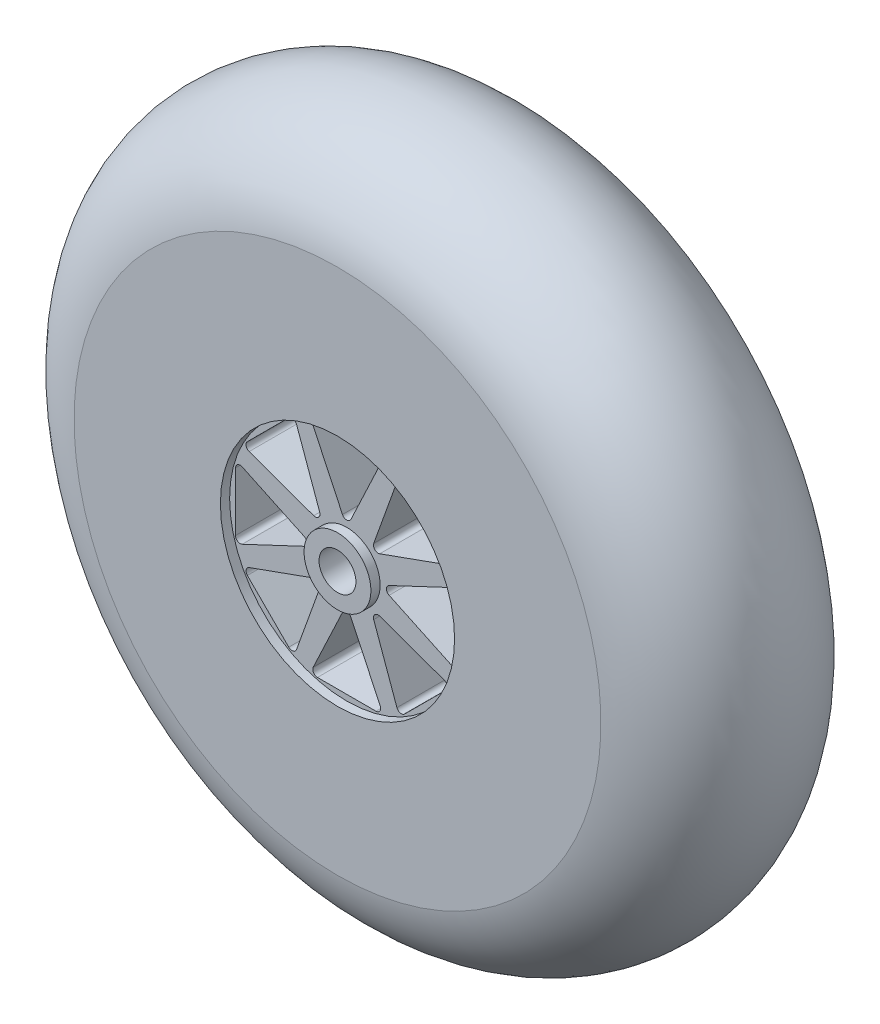
SolidWorks part; units mm, degrees
material "Rubber"
ref_plane "Front Plane" through (0, 0, 0) normal (0, 0, 1) x (1, 0, 0)
ref_plane "Top Plane" through (0, 0, 0) normal (0, 1, 0) x (1, 0, 0)
ref_plane "Right Plane" through (0, 0, 0) normal (1, 0, 0) x (0, 0, -1)
sketch "Sketch1" plane through (0, 0, 0) normal (1, 0, 0) x (0, 0, -1)
  line L0 (0, 28.575) -> (0, 2)
  line L1 (22.225, 28.575) -> (22.225, 2)
  line L2 (11.1125, 38.1) -> (11.1125, 0) construction
  line L3 (22.225, 0) -> (0, 0) construction
  line L4 (22.225, 2) -> (0, 2)
  arc A0 (0, 28.575) -> (22.225, 28.575) centre (11.1125, 26.8552) cw
  dimension "D3" = 38.1
  dimension "D1" = 28.575
  dimension "D2" = 22.225
  dimension "D4" = 2
revolve "Revolve1" add sketch "Sketch1" angle 360 about L3
sketch "Sketch2" plane through (0, 0, 0) normal (0, 0, 1) x (1, 0, 0)
  circle A0 centre (0, 0) radius 12.7
  circle A1 centre (0, 0) radius 3.625
  dimension "D1" = 25.4
  dimension "D2" = 7.25
extrude "Cut-Extrude1" cut sketch "Sketch2" against normal blind 1
sketch "Sketch3" plane through (0, 0, -1) normal (0, 0, 1) x (1, 0, 0)
  line L0 (0, 12.7) -> (0, 3.625) construction
  line L1 (-0.4595, 4.6001) -> (-3.6345, 11.337)
  line L2 (-3.175, 12.0616) -> (3.175, 12.0616)
  line L3 (0.4595, 4.6001) -> (3.6345, 11.337)
  line L4 (3.5777, 2.9278) -> (10.5865, 5.4465)
  line L5 (6.2838, 10.7739) -> (10.7739, 6.2838)
  line L6 (2.9278, 3.5777) -> (5.4465, 10.5865)
  line L7 (4.6001, -0.4595) -> (11.337, -3.6345)
  line L8 (12.0616, 3.175) -> (12.0616, -3.175)
  line L9 (4.6001, 0.4595) -> (11.337, 3.6345)
  line L10 (2.9278, -3.5777) -> (5.4465, -10.5865)
  line L11 (10.7739, -6.2838) -> (6.2838, -10.7739)
  line L12 (3.5777, -2.9278) -> (10.5865, -5.4465)
  line L13 (-0.4595, -4.6001) -> (-3.6345, -11.337)
  line L14 (3.175, -12.0616) -> (-3.175, -12.0616)
  line L15 (0.4595, -4.6001) -> (3.6345, -11.337)
  line L16 (-3.5777, -2.9278) -> (-10.5865, -5.4465)
  line L17 (-6.2838, -10.7739) -> (-10.7739, -6.2838)
  line L18 (-2.9278, -3.5777) -> (-5.4465, -10.5865)
  line L19 (-4.6001, 0.4595) -> (-11.337, 3.6345)
  line L20 (-12.0616, -3.175) -> (-12.0616, 3.175)
  line L21 (-4.6001, -0.4595) -> (-11.337, -3.6345)
  line L22 (-2.9278, 3.5777) -> (-5.4465, 10.5865)
  line L23 (-10.7739, 6.2838) -> (-6.2838, 10.7739)
  line L24 (-3.5777, 2.9278) -> (-10.5865, 5.4465)
  circle A0 centre (0, 0) radius 12.7 construction
  circle A1 centre (0, 0) radius 12.7 construction
  circle A2 centre (0, 0) radius 3.625 construction
  arc A3 (-3.175, 12.0616) -> (-3.6345, 11.337) centre (-3.175, 11.5536) ccw
  arc A4 (3.175, 12.0616) -> (3.6345, 11.337) centre (3.175, 11.5536) cw
  arc A5 (0.4595, 4.6001) -> (-0.4595, 4.6001) centre (0, 4.8166) cw
  arc A6 (3.5777, 2.9278) -> (2.9278, 3.5777) centre (3.4059, 3.4059) cw
  arc A7 (10.7739, 6.2838) -> (10.5865, 5.4465) centre (10.4147, 5.9245) cw
  arc A8 (6.2838, 10.7739) -> (5.4465, 10.5865) centre (5.9245, 10.4147) ccw
  arc A9 (4.6001, -0.4595) -> (4.6001, 0.4595) centre (4.8166, 0) cw
  arc A10 (12.0616, -3.175) -> (11.337, -3.6345) centre (11.5536, -3.175) cw
  arc A11 (12.0616, 3.175) -> (11.337, 3.6345) centre (11.5536, 3.175) ccw
  arc A12 (2.9278, -3.5777) -> (3.5777, -2.9278) centre (3.4059, -3.4059) cw
  arc A13 (6.2838, -10.7739) -> (5.4465, -10.5865) centre (5.9245, -10.4147) cw
  arc A14 (10.7739, -6.2838) -> (10.5865, -5.4465) centre (10.4147, -5.9245) ccw
  arc A15 (-0.4595, -4.6001) -> (0.4595, -4.6001) centre (0, -4.8166) cw
  arc A16 (-3.175, -12.0616) -> (-3.6345, -11.337) centre (-3.175, -11.5536) cw
  arc A17 (3.175, -12.0616) -> (3.6345, -11.337) centre (3.175, -11.5536) ccw
  arc A18 (-3.5777, -2.9278) -> (-2.9278, -3.5777) centre (-3.4059, -3.4059) cw
  arc A19 (-10.7739, -6.2838) -> (-10.5865, -5.4465) centre (-10.4147, -5.9245) cw
  arc A20 (-6.2838, -10.7739) -> (-5.4465, -10.5865) centre (-5.9245, -10.4147) ccw
  arc A21 (-4.6001, 0.4595) -> (-4.6001, -0.4595) centre (-4.8166, 0) cw
  arc A22 (-12.0616, 3.175) -> (-11.337, 3.6345) centre (-11.5536, 3.175) cw
  arc A23 (-12.0616, -3.175) -> (-11.337, -3.6345) centre (-11.5536, -3.175) ccw
  arc A24 (-2.9278, 3.5777) -> (-3.5777, 2.9278) centre (-3.4059, 3.4059) cw
  arc A25 (-6.2838, 10.7739) -> (-5.4465, 10.5865) centre (-5.9245, 10.4147) cw
  arc A26 (-10.7739, 6.2838) -> (-10.5865, 5.4465) centre (-10.4147, 5.9245) ccw
  point P14 (-3.976, 12.0616)
  point P18 (0, 12.0616)
  point P86 (0, 0)
  dimension "D1" = 0.508
  dimension "D2" = 0.508
  dimension "D3" = 6.35
  dimension "D4" = 8
extrude "Cut-Extrude2" cut sketch "Sketch3" against normal blind 9.525
